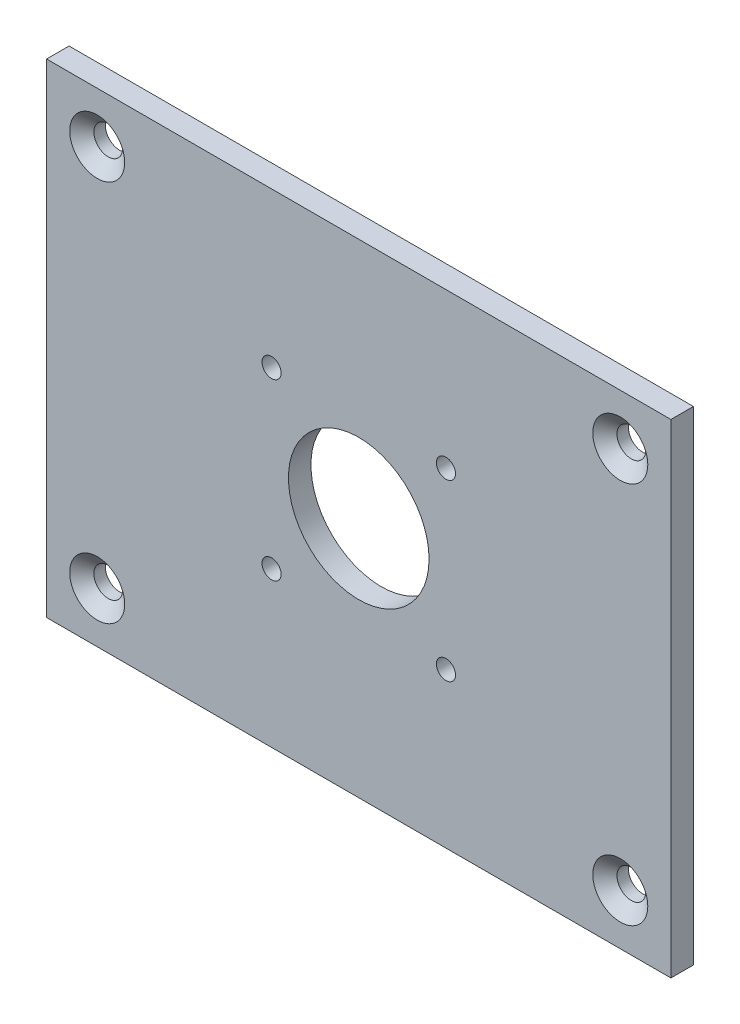
SolidWorks part; units mm, degrees
ref_plane "Front Plane" through (0, 0, 0) normal (0, 0, 1) x (1, 0, 0)
ref_plane "Top Plane" through (0, 0, 0) normal (0, 1, 0) x (1, 0, 0)
ref_plane "Right Plane" through (0, 0, 0) normal (1, 0, 0) x (0, 0, -1)
sketch "Sketch1" plane through (0, 0, 0) normal (0, 0, 1) x (1, 0, 0)
  line L1 (0, 0) -> (111, 0)
  line L2 (0, 0) -> (0, 86)
  line L3 (0, 86) -> (111, 86)
  line L4 (111, 0) -> (111, 86)
  dimension "D1" = 111
  dimension "D2" = 86
extrude "base" add sketch "Sketch1" along normal blind 4
sketch "way outline" plane through (0, 0, 4) normal (0, 0, 1) x (1, 0, 0)
  line L0 (0, 43) -> (18, 43)
  line L1 (18, 68) -> (93, 68)
  line L2 (18, 68) -> (18, 18)
  line L3 (18, 18) -> (93, 18)
  line L4 (93, 68) -> (93, 18)
  line L5 (0, 86) -> (0, 0) construction
  line L6 (55.5, 68) -> (55.5, 86)
  line L7 (111, 86) -> (0, 86) construction
  point P12 (0, 0)
  dimension "D1" = 50
  dimension "D2" = 75
hole_wizard "nema 17 screw hole pattern" positions "Sketch3" profile "Sketch4" hole size "M3" standard "ANSI Metric" end condition through all
sketch "Sketch3" plane through (0, 0, 4) normal (0, 0, 1) x (1, 0, 0)
  line L1 (40, 58.5) -> (71, 58.5)
  line L2 (40, 58.5) -> (40, 27.5)
  line L3 (40, 27.5) -> (71, 27.5)
  line L4 (71, 58.5) -> (71, 27.5)
  point P1 (40, 58.5)
  point P2 (71, 27.5)
  point P69 (40, 27.5)
  point P70 (71, 58.5)
  point P71 (40, 43)
  point P75 (55.5, 58.5)
  dimension "D1" = 31
sketch "Sketch4" plane through (40, 58.5, 4) normal (1, 0, 0) x (0, -1, 0)
  line L0 (0, 0) -> (0, 4)
  line L1 (0, 4) -> (1.7, 4)
  line L2 (1.7, 4) -> (1.7, 0)
  line L5 (1.7, 0) -> (0, 0)
  line L11 (0, -6.35) -> (0, 107.95) construction
  dimension "Thru Hole Dia." = 3.4
  dimension "Thru Hole Depth" = 4
sketch "Sketch5" plane through (0, 0, 4) normal (0, 0, 1) x (1, 0, 0)
  circle A0 centre (55.5, 43) radius 12.5
  point P2 (0, 0)
  point P4 (0, 0)
  dimension "D1" = 25
extrude "motor shaft cleareance" cut sketch "Sketch5" against normal through all
hole_wizard "wood screw hole pattern" positions "Sketch6" profile "Sketch7" countersink size "#10" standard "ANSI Inch" end condition through all
sketch "Sketch6" plane through (0, 0, 4) normal (0, 0, 1) x (1, 0, 0)
  line L1 (9, 77) -> (102, 77)
  line L2 (9, 77) -> (9, 9)
  line L3 (9, 9) -> (102, 9)
  line L4 (102, 77) -> (102, 9)
  line L8 (9, 43) -> (0, 43)
  line L10 (55.5, 77) -> (55.5, 86)
  point P1 (9, 77)
  point P2 (102, 9)
  point P199 (9, 9)
  point P200 (102, 77)
  dimension "D1" = 9
  dimension "D2" = 9
sketch "Sketch7" plane through (9, 77, 4) normal (1, 0, 0) x (0, -1, 0)
  line L0 (0, 0) -> (0, 4)
  line L1 (0, 4) -> (2.5527, 4)
  line L2 (2.5527, 4) -> (2.5527, 1.9608)
  line L3 (2.5527, 1.9608) -> (4.8895, 0)
  line L5 (4.8895, 0) -> (0, 0)
  line L6 (-2.5527, 1.9608) -> (-4.8895, 0) construction
  line L11 (0, -6.35) -> (0, 107.95) construction
  dimension "Thru Hole Dia." = 5.1054
  dimension "Thru Hole Depth" = 4
  dimension "Near C'Sink Dia." = 9.779
  dimension "Near C'Sink Angle" = 100
equation "\"board_thickness\" = 18mm"
equation "\"way_width\"= 75mm"
equation "\"way_thickness\"= 50mm"
equation "\"radial_clearance\"= 0.1mm"
equation "\"slider_width\"= \"way_width\"-2* \"radial_clearance\""
equation "\"slider_thickness\" = \"way_thickness\" - 2 * \"radial_clearance\""
equation "\"column_width\"= \"way_width\" + 2 * \"board_thickness\""
equation "\"boxway_slot_width\" = 50mm"
equation "\"keeper_rail_width\" = (\"column_width\" - \"boxway_slot_width\")/2"
equation "\"slider_length\" = 125mm"
equation "\"nut_diameter\"= 22mm"
equation "\"nut_length\"= 15mm"
equation "\"leadscrew_diameter\"= 10mm"
equation "\"leadscrew_radial_clearance\"= 1mm"
equation "\"bearing_bolt_pattern_width\" = 30mm"
equation "\"bearing_bolt_pattern_height\" = 75mm"
equation "\"desktop_bolt_pattern_width\" = 30mm"
equation "\"desktop_bolt_pattern_height\" = 30mm"
equation "\"bearing_bolt_nut_counterbore_diameter\" = 12mm"
equation "\"bearing_bolt_nut_counterbore_depth\"= 10mm"
equation "\"desktop_depth\"= 500mm"
equation "\"desktop_width\"= 650mm"
equation "\"desktop_thickness\"= 18mm"
equation "\"leg_height\"=100mm"
equation "\"leg_width\"=18mm"
equation "\"leg_length\"=500mm"
equation "\"lap_joint_height\" = 50mm"
equation "\"lap_dowel_diameter\"= 8mm"
equation "\"lap_dowel_hole_z_spacing\"=30"
equation "\"D1@Sketch1\"=\"column_width\""
equation "\"D2@Sketch1\"=2*\"board_thickness\"+\"way_thickness\""
equation "\"D1@way outline\" = \"way_thickness\""
equation "\"D2@way outline\" = \"way_width\""
equation "\"D2@Sketch6\"=0.5 * \"board_thickness\""
